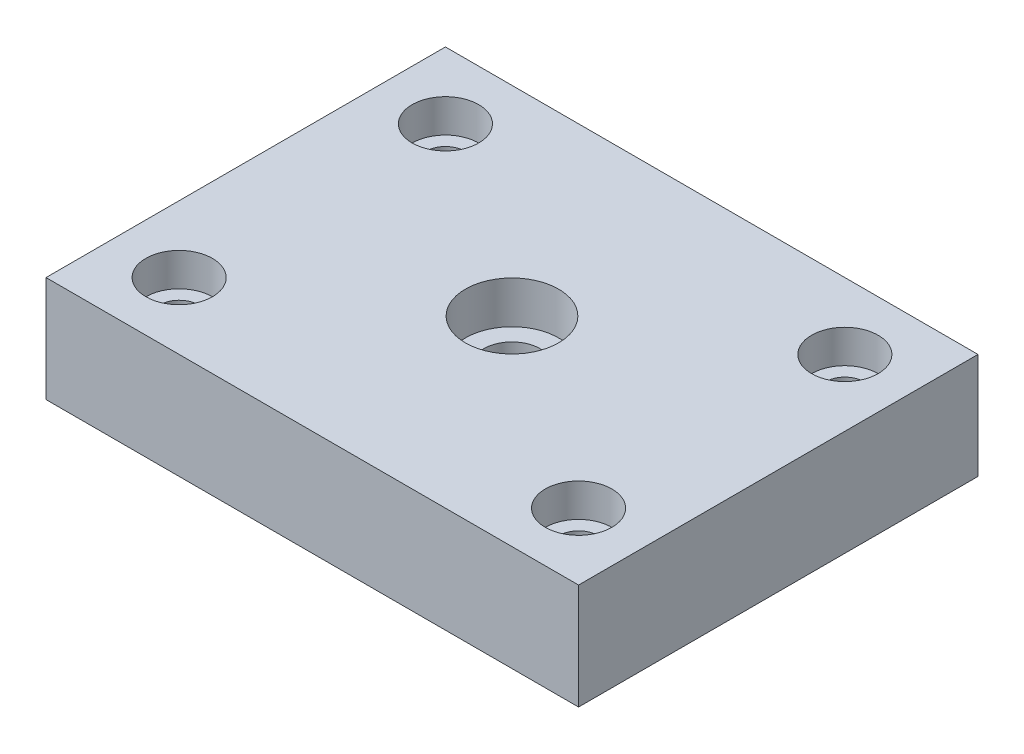
SolidWorks part; units mm, degrees
note: The reader was unsure of these and kept them because the rebuilt part matched: thickness of "Base-Flange1", "Sheet-Metal1", "Sheet-Metal2", "Sheet-Metal3".
material "6061 Alloy"
ref_plane "Front Plane" through (0, 0, 0) normal (0, 0, 1) x (1, 0, 0)
ref_plane "Top Plane" through (0, 0, 0) normal (0, 1, 0) x (1, 0, 0)
ref_plane "Right Plane" through (0, 0, 0) normal (1, 0, 0) x (0, 0, -1)
sketch "Sketch1" plane through (0, 0, 0) normal (0, 1, 0) x (1, 0, 0)
  line L1 (-40, -30) -> (40, -30)
  line L2 (-40, -30) -> (-40, 30)
  line L3 (-40, 30) -> (40, 30)
  line L4 (40, -30) -> (40, 30)
  line L5 (-40, -30) -> (40, 30) construction
  line L6 (-40, 30) -> (40, -30) construction
  point P0 (0, 0)
  dimension "D1" = 60
  dimension "D2" = 80
base flange "Base-Flange1" sketch "Sketch1" thickness 15.875 reverse thickness direction no parameters "D1"=7.5
hole_wizard "CBORE for M5 SHCS1" positions "Sketch6" profile "Sketch7" counterbore size "M5" standard "ANSI Metric" end condition through all
sketch "Sketch6" plane through (0, 0, 0) normal (0, 1, 0) x (1, 0, 0)
  line L1 (-30, 20) -> (30, 20)
  line L2 (-30, 20) -> (-30, -20)
  line L3 (-30, -20) -> (30, -20)
  line L4 (30, 20) -> (30, -20)
  line L5 (-30, 20) -> (30, -20) construction
  line L6 (-30, -20) -> (30, 20) construction
  point P0 (-30, -20)
  point P2 (-30, 20)
  point P4 (30, 20)
  point P6 (30, -20)
  dimension "D1" = 40
  dimension "D2" = 60
sketch "Sketch7" plane through (-30, 0, 20) normal (1, 0, 0) x (0, 0, 1)
  line L0 (0, 0) -> (0, 15.875)
  line L1 (0, 15.875) -> (2.9, 15.875)
  line L3 (2.9, 15.875) -> (2.9, 5)
  line L4 (2.9, 5) -> (5, 5)
  line L5 (5, 5) -> (5, 0)
  line L7 (5, 0) -> (0, 0)
  line L11 (0, -6.35) -> (0, 107.95) construction
  dimension "Thru Hole Dia." = 5.8
  dimension "Thru Hole Depth" = 15.875
  dimension "C'Bore Dia." = 10
  dimension "C'Bore Depth" = 5
hole_wizard "3/8-24 Tapped Hole1" positions "Sketch8" profile "Sketch9" tap size "3/8-24" standard "ANSI Inch" end condition through all
sketch "Sketch8" plane through (0, 0, 0) normal (0, 1, 0) x (1, 0, 0)
  point P0 (0, 0)
sketch "Sketch9" plane through (0, 0, 0) normal (1, 0, 0) x (0, 0, 1)
  line L0 (0, 0) -> (0, 15.875)
  line L1 (0, 15.875) -> (4.2164, 15.875)
  line L2 (4.2164, 15.875) -> (4.2164, 6.35)
  line L3 (4.2164, 6.35) -> (7, 6.35)
  line L4 (7, 6.35) -> (7, 0)
  line L5 (7, 0) -> (0, 0)
  line L11 (0, -6.35) -> (0, 107.95) construction
  dimension "Thru Tap Drill Dia." = 8.4328
  dimension "Thru Tap Drill Depth" = 15.875
cosmetic thread "Hole Thread3"
sketch "Bend-Lines1" [suppressed]
sketch "Bounding-Box1" [suppressed] plane through (0, 0, 0) normal (0, 1, 0) x (1, 0, 0)
sheet metal parameters "Sheet-Metal1" thickness 15.875 parameters "D1"=7.5, "D7"=10
flat pattern "Flat-Pattern1" [suppressed]
sketch "Bend-Lines2" plane through (0, 0, 0) normal (0, 1, 0) x (1, 0, 0)
sketch3d "Bounding-Box2" [suppressed]
  line L0 (-40, 30, 0) -> (40, 30, 0) construction
  line L1 (-40, -30, 0) -> (40, -30, 0) construction
  line L2 (-40, 30, 0) -> (-40, -30, 0) construction
  line L3 (40, 30, 0) -> (40, -30, 0) construction
sheet metal parameters "Sheet-Metal2" thickness 15.875 parameters "D1"=7.5, "D7"=10
flat pattern "Flat-Pattern1"
sketch "Bend-Lines2" plane through (0, 0, 0) normal (0, 1, 0) x (1, 0, 0)
sketch3d "Bounding-Box2" [suppressed]
  line L0 (40, 30, 0) -> (-40, 30, 0) construction
  line L1 (40, -30, 0) -> (-40, -30, 0) construction
  line L2 (40, 30, 0) -> (40, -30, 0) construction
  line L3 (-40, 30, 0) -> (-40, -30, 0) construction
sheet metal parameters "Sheet-Metal3" thickness 15.875 parameters "D1"=7.5, "D7"=10
flat pattern "Flat-Pattern1"
sketch "Bend-Lines2" plane through (0, 0, 0) normal (0, 1, 0) x (1, 0, 0)
sketch3d "Bounding-Box2" [suppressed]
  line L0 (40, 30, 0) -> (-40, 30, 0) construction
  line L1 (40, -30, 0) -> (-40, -30, 0) construction
  line L2 (40, 30, 0) -> (40, -30, 0) construction
  line L3 (-40, 30, 0) -> (-40, -30, 0) construction
